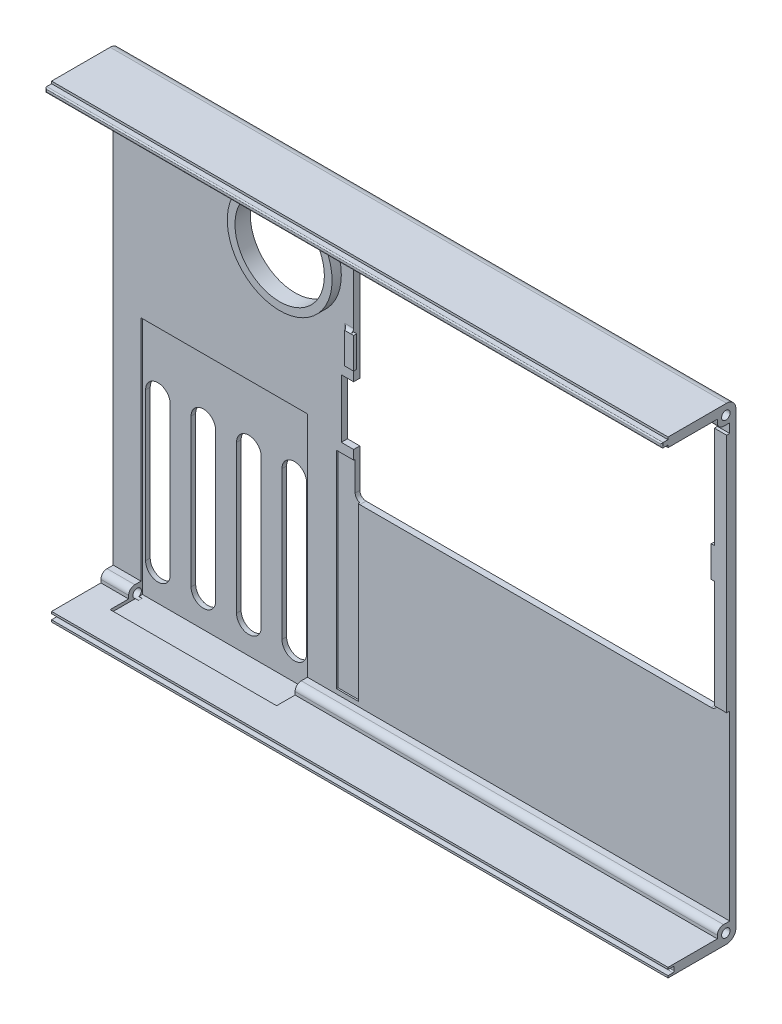
SolidWorks part; units mm, degrees
ref_plane "Front Plane" through (0, 0, 0) normal (0, 0, 1) x (1, 0, 0)
ref_plane "Top Plane" through (0, 0, 0) normal (0, 1, 0) x (1, 0, 0)
ref_plane "Right Plane" through (0, 0, 0) normal (1, 0, 0) x (0, 0, -1)
sketch "Sketch1" plane through (0, 0, 0) normal (0, 0, 1) x (1, 0, 0)
  line L1 (105, -90.3987) -> (-95, -90.3987)
  line L2 (105, -90.3987) -> (105, 61.6013)
  line L3 (105, 61.6013) -> (-95, 61.6013)
  line L4 (-95, -90.3987) -> (-95, 61.6013)
  line L5 (105, -90.3987) -> (-95, 61.6013) construction
  line L6 (105, 61.6013) -> (-95, -90.3987) construction
  point P0 (5, -14.3987)
  dimension "D1" = 200
  dimension "D2" = 152
extrude "body" add sketch "Sketch1" along normal blind 2
sketch "Sketch3" plane through (0, 0, 0) normal (0, 0, -1) x (-1, 0, 0)
  line L0 (95, -54.3987) -> (-105, -54.3987) construction
  line L1 (95, 61.6013) -> (95, -90.3987) construction
  line L2 (-105, -90.3987) -> (-105, 61.6013) construction
  line L3 (66.25, -78.3987) -> (66.25, -30.3987) construction
  line L4 (62.25, -78.3987) -> (62.25, -30.3987)
  line L5 (70.25, -78.3987) -> (70.25, -30.3987)
  line L6 (95, -30.3987) -> (-105, -30.3987) construction
  line L7 (81, -78.3987) -> (81, -30.3987) construction
  line L8 (95, -78.3987) -> (-105, -78.3987) construction
  line L9 (77, -78.3987) -> (77, -30.3987)
  line L10 (85, -78.3987) -> (85, -30.3987)
  line L11 (51.5, -78.3987) -> (51.5, -30.3987) construction
  line L12 (47.5, -78.3987) -> (47.5, -30.3987)
  line L13 (55.5, -78.3987) -> (55.5, -30.3987)
  line L14 (36.75, -78.3987) -> (36.75, -30.3987) construction
  line L15 (32.75, -78.3987) -> (32.75, -30.3987)
  line L16 (40.75, -78.3987) -> (40.75, -30.3987)
  line L17 (95, -90.3987) -> (95, 61.6013) construction
  line L18 (-105, 61.6013) -> (95, 61.6013) construction
  line L19 (95, -90.3987) -> (-105, -90.3987) construction
  line L20 (-105, -90.3987) -> (-105, 61.6013) construction
  circle A0 centre (38, 34.1013) radius 14.5
  arc A1 (62.25, -78.3987) -> (70.25, -78.3987) centre (66.25, -78.3987) ccw
  arc A2 (70.25, -30.3987) -> (62.25, -30.3987) centre (66.25, -30.3987) ccw
  arc A3 (77, -78.3987) -> (85, -78.3987) centre (81, -78.3987) ccw
  arc A4 (85, -30.3987) -> (77, -30.3987) centre (81, -30.3987) ccw
  arc A5 (47.5, -78.3987) -> (55.5, -78.3987) centre (51.5, -78.3987) ccw
  arc A6 (55.5, -30.3987) -> (47.5, -30.3987) centre (51.5, -30.3987) ccw
  arc A7 (32.75, -78.3987) -> (40.75, -78.3987) centre (36.75, -78.3987) ccw
  arc A8 (40.75, -30.3987) -> (32.75, -30.3987) centre (36.75, -30.3987) ccw
  point P10 (66.25, -54.3987)
  point P21 (81, -54.3987)
  point P27 (51.5, -54.3987)
  point P34 (36.75, -54.3987)
  dimension "D1" = 29
  dimension "D2" = 27.5
  dimension "D3" = 57
  dimension "D4" = 10
  dimension "D5" = 12
  dimension "D6" = 24
  dimension "D7" = 6.75
  dimension "D8" = 8
  dimension "D9" = 8
  dimension "D10" = 8
  dimension "D11" = 8
  dimension "D12" = 6.75
  dimension "D13" = 52.25
  dimension "D14" = 6.75
extrude "fan_exhaust_grill" cut sketch "Sketch3" against normal through all
sketch "Sketch12" plane through (0, 0, 2) normal (0, 0, 1) x (1, 0, 0)
  line L0 (-95, -90.3987) -> (-95, 61.6013) construction
  line L1 (105, -90.3987) -> (-95, -90.3987)
  line L2 (105, -90.3987) -> (105, -84.3987)
  line L3 (105, -84.3987) -> (-95, -84.3987)
  line L4 (-95, -90.3987) -> (-95, -84.3987)
  line L6 (105, 61.6013) -> (-95, 61.6013)
  line L7 (105, 61.6013) -> (105, 55.6013)
  line L8 (105, 55.6013) -> (-95, 55.6013)
  line L9 (-95, 61.6013) -> (-95, 55.6013)
  dimension "D1" = 6
  dimension "D2" = 6
extrude "side_walls" add sketch "Sketch12" along normal blind 20
sketch "Sketch14" plane through (105, 0, 0) normal (1, 0, 0) x (0, 0, -1)
  line L0 (-22, -90.3987) -> (0, -90.3987) construction
  line L1 (0, -90.3987) -> (0, 61.6013) construction
  line L2 (-22, 61.6013) -> (0, 61.6013) construction
  circle A0 centre (-3.25, -87.1487) radius 1.375
  circle A1 centre (-3.25, 58.3513) radius 1.375
  dimension "D1" = 2.75
  dimension "D2" = 2.75
  dimension "D3" = 3.25
  dimension "D4" = 3.25
  dimension "D5" = 3.25
  dimension "D6" = 3.25
  dimension "D7" = 145.5
extrude "mount_holes_l" cut sketch "Sketch14" against normal blind 10 and the other way through all
sketch "Sketch16" plane through (-95, 0, 0) normal (-1, 0, 0) x (0, 0, 1)
  line L0 (0, -90.3987) -> (0, 61.6013) construction
  line L2 (22, 61.6013) -> (0, 61.6013) construction
  line L3 (22, -90.3987) -> (0, -90.3987) construction
  circle A0 centre (3.25, -87.1487) radius 1.375
  circle A1 centre (3.25, 58.3513) radius 1.375
  dimension "D1" = 2.75
  dimension "D4" = 2.75
  dimension "D2" = 3.25
  dimension "D3" = 3.25
  dimension "D5" = 3.25
  dimension "D6" = 3.25
extrude "mount_holes_r" cut sketch "Sketch16" against normal blind 10
sketch "Sketch18" plane through (105, 0, 0) normal (1, 0, 0) x (0, 0, -1)
  line L1 (-22, -84.3987) -> (-6, -84.3987)
  line L2 (-22, -84.3987) -> (-22, -87.3987)
  line L3 (-22, -87.3987) -> (-6, -87.3987)
  line L4 (-6, -84.3987) -> (-6, -87.3987)
  line L5 (-22, 55.6013) -> (-6, 55.6013)
  line L6 (-22, 55.6013) -> (-22, 58.6013)
  line L7 (-22, 58.6013) -> (-6, 58.6013)
  line L8 (-6, 55.6013) -> (-6, 58.6013)
  dimension "D1" = 3
  dimension "D2" = 16
  dimension "D3" = 3
  dimension "D4" = 16
extrude "wall_reduce" cut sketch "Sketch18" against normal through all
sketch "Sketch19" plane through (0, 0, 22) normal (0, 0, 1) x (1, 0, 0)
  line L0 (-95, -90.3987) -> (-95, 61.6013) construction
  line L1 (-95, -89.7487) -> (105, -89.7487)
  line L2 (-95, -89.7487) -> (-95, -88.0487)
  line L3 (-95, -88.0487) -> (105, -88.0487)
  line L4 (105, -89.7487) -> (105, -88.0487)
  line L5 (105, -90.3987) -> (105, 61.6013) construction
  line L6 (-95, -90.3987) -> (105, -90.3987) construction
  line L7 (-95, -87.3987) -> (105, -87.3987) construction
  dimension "D1" = 0.65
  dimension "D2" = 1.7
  dimension "D3" = 0.65
extrude "groove" cut sketch "Sketch19" against normal blind 2
sketch "Sketch20" plane through (0, 0, 22) normal (0, 0, 1) x (1, 0, 0)
  line L0 (-95, -90.3987) -> (-95, 61.6013) construction
  line L1 (-95, 59.3513) -> (105, 59.3513)
  line L2 (-95, 59.3513) -> (-95, 60.8513)
  line L3 (-95, 60.8513) -> (105, 60.8513)
  line L4 (105, 59.3513) -> (105, 60.8513)
  line L5 (105, -90.3987) -> (105, 61.6013) construction
  line L6 (105, 61.6013) -> (-95, 61.6013) construction
  dimension "D1" = 0.75
  dimension "D2" = 1.5
extrude "notch" add sketch "Sketch20" along normal blind 2
sketch "Sketch21" plane through (0, 0, 2) normal (0, 0, 1) x (1, 0, 0)
  line L0 (105, -90.3987) -> (105, 61.6013) construction
  line L1 (101, -27.3987) -> (-17, -27.3987)
  line L2 (101, -27.3987) -> (101, 55.1013)
  line L3 (101, 55.1013) -> (-17, 55.1013)
  line L4 (-17, -27.3987) -> (-17, 55.1013)
  line L5 (105, 61.6013) -> (-95, 61.6013) construction
  dimension "D1" = 118
  dimension "D2" = 82.5
  dimension "D3" = 4
  dimension "D4" = 6.5
extrude "batt_cut" cut sketch "Sketch21" against normal through all
fillet "Fillet1" radius 3 2 edges at (5, -90.3987, 0) (5, 61.6013, 0)
fillet "Fillet2" radius 2 2 edges at (5, -84.3987, 6) (5, 55.6013, 6)
fillet "Fillet3" radius 0.4 6 edges at (5, 60.8513, 24) (105, 60.1013, 24) (5, 59.3513, 24) (-95, 60.1013, 24) (5, -89.7487, 20) (5, -88.0487, 20)
fillet "Fillet4" radius 2 4 edges at (-17, -27.3987, 1) (101, -27.3987, 1) (101, 55.1013, 1) (-17, 55.1013, 1)
sketch "Sketch22" plane through (0, 0, 2) normal (0, 0, 1) x (1, 0, 0)
  circle A0 centre (-38, 34.1013) radius 14.5
  circle A1 centre (-38, 34.1013) radius 17
  dimension "D1" = 29
  dimension "D2" = 34
extrude "fan_hole_supp" add sketch "Sketch22" along normal blind 3
sketch "Sketch23" plane through (0, 0, 2) normal (0, 0, 1) x (1, 0, 0)
  line L0 (105, -90.3987) -> (105, 61.6013) construction
  line L1 (105, 52.6013) -> (101, 52.6013)
  line L2 (105, 52.6013) -> (105, -25.3987)
  line L3 (105, -25.3987) -> (101, -25.3987)
  line L4 (101, 52.6013) -> (101, -25.3987)
  arc A0 (99, -27.3987) -> (101, -25.3987) centre (99, -25.3987) ccw construction
  dimension "D1" = 78
  dimension "D2" = 4
extrude "batt_cut_supp" add sketch "Sketch23" along normal blind 1
sketch "Sketch24" plane through (0, 0, 2) normal (0, 0, 1) x (1, 0, 0)
  line L0 (-95, -90.3987) -> (-95, 61.6013) construction
  line L1 (-86, -10.3987) -> (-32, -10.3987)
  line L2 (-86, -10.3987) -> (-86, -88.3987)
  line L3 (-86, -88.3987) -> (-32, -88.3987)
  line L4 (-32, -10.3987) -> (-32, -88.3987)
  line L5 (-95, -90.3987) -> (105, -90.3987) construction
  line L7 (-22.5, -15.8987) -> (-15.5, -15.8987)
  line L8 (-22.5, -15.8987) -> (-22.5, -82.8987)
  line L9 (-22.5, -82.8987) -> (-15.5, -82.8987)
  line L10 (-15.5, -15.8987) -> (-15.5, -82.8987)
  dimension "D1" = 9
  dimension "D2" = 2
  dimension "D3" = 54
  dimension "D4" = 78
  dimension "D5" = 9.5
  dimension "D6" = 7
  dimension "D7" = 67
  dimension "D8" = 5.5
  dimension "D9" = 5.5
extrude "Cut-Extrude1" cut sketch "Sketch24" against normal blind 10.5 from offset 10
sketch "Sketch25" plane through (0, 0, 2) normal (0, 0, 1) x (1, 0, 0)
  line L7 (-17, 53.1013) -> (-17, -15.8987) construction
  line L8 (-17, 6.1013) -> (-21, 6.1013)
  line L9 (-17, 6.1013) -> (-17, -12.8987)
  line L10 (-17, -12.8987) -> (-21, -12.8987)
  line L11 (-21, 6.1013) -> (-21, -12.8987)
  line L12 (-15, -27.3987) -> (99, -27.3987) construction
  dimension "D1" = 14.5
  dimension "D2" = 19
  dimension "D3" = 4
extrude "Cut-Extrude2" cut sketch "Sketch25" against normal through all
sketch "Sketch26" plane through (0, 0, 2) normal (0, 0, 1) x (1, 0, 0)
  line L0 (-17, 53.1013) -> (-17, 6.1013) construction
  line L1 (-17, 20.1013) -> (-19, 20.1013)
  line L2 (-17, 20.1013) -> (-17, 10.1013)
  line L3 (-17, 10.1013) -> (-19, 10.1013)
  line L4 (-19, 20.1013) -> (-19, 10.1013)
  line L10 (99, 55.1013) -> (-15, 55.1013) construction
  dimension "D4" = 2
  dimension "D5" = 10
  dimension "D6" = 35
extrude "Boss-Extrude1" add sketch "Sketch26" along normal blind 1
sketch "Sketch27" plane through (-17, 0, 0) normal (1, 0, 0) x (0, 0, -1)
  line L0 (-3, 10.1013) -> (-3, 20.1013) construction
  line L1 (-3, 20.1013) -> (-2, 20.1013)
  line L2 (-3, 20.1013) -> (-3, 10.1013)
  line L3 (-3, 10.1013) -> (-2, 10.1013)
  line L4 (-2, 20.1013) -> (-2, 10.1013)
  line L5 (-3, 20.1013) -> (-2, 20.1013) construction
extrude "Boss-Extrude2" add sketch "Sketch27" along normal blind 1
sketch "Sketch28" plane through (101, 0, 0) normal (-1, 0, 0) x (0, 0, 1)
  line L0 (0, -25.3987) -> (0, 53.1013) construction
  line L1 (2, 9.6013) -> (3, 9.6013)
  line L2 (2, 9.6013) -> (2, 19.6013)
  line L3 (2, 19.6013) -> (3, 19.6013)
  line L4 (3, 9.6013) -> (3, 19.6013)
  line L5 (3, 52.6013) -> (2, 52.6013) construction
  dimension "D1" = 1
  dimension "D2" = 2
  dimension "D3" = 10
  dimension "D4" = 33
extrude "Boss-Extrude3" add sketch "Sketch28" along normal blind 1
fillet "Fillet5" radius 1 3 edges at (-18, 20.1013, 2) (-18, 10.1013, 2) (-19, 15.1013, 2)
